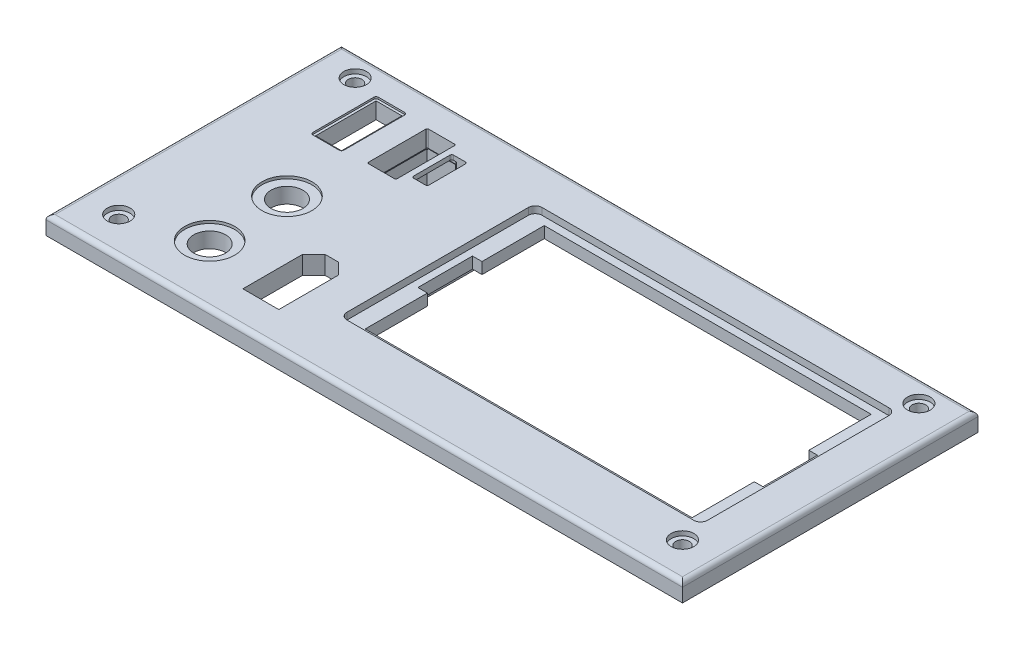
SolidWorks part; units mm, degrees
ref_plane "Спереди" through (0, 0, 0) normal (0, 0, 1) x (1, 0, 0)
ref_plane "Сверху" through (0, 0, 0) normal (0, 1, 0) x (1, 0, 0)
ref_plane "Справа" through (0, 0, 0) normal (1, 0, 0) x (0, 0, -1)
sketch "Эскиз1" plane through (0, 0, 0) normal (0, 1, 0) x (1, 0, 0)
  line L1 (-60, 30) -> (80, 30)
  line L2 (-60, 30) -> (-60, -35)
  line L3 (-60, -35) -> (80, -35)
  line L4 (80, 30) -> (80, -35)
  line L5 (-60, 30) -> (80, -35) construction
  line L6 (-60, -35) -> (80, 30) construction
  point P0 (0, 0)
  dimension "D1" = 65
  dimension "D2" = 140
extrude "Передняя панель основа" add sketch "Эскиз1" along normal blind 4
sketch "Эскиз2" plane through (0, 4, 0) normal (0, 1, 0) x (1, 0, 0)
  line L1 (71, 20.9) -> (-8.3, 20.9)
  line L2 (71, 20.9) -> (71, -22)
  line L3 (71, -22) -> (-8.3, -22)
  line L4 (-8.3, 20.9) -> (-8.3, -22)
  line L5 (71, 20.9) -> (-8.3, -22) construction
  line L6 (71, -22) -> (-8.3, 20.9) construction
  point P0 (31.35, -0.55)
  dimension "D1" = 42.9
  dimension "D2" = 79.3
  dimension "D3" = 13
  dimension "D4" = 9
extrude "Внешняя рамка модуля" cut sketch "Эскиз2" against normal blind 1.5
fillet "Уголки скругления рамки выреза модуля" radius 1.5 4 edges at (71, 3.25, 22) (-8.3, 3.25, 22) (71, 3.25, -20.9) (-8.3, 3.25, -20.9)
sketch "Эскиз3" plane through (0, 2.5, 0) normal (0, 1, 0) x (1, 0, 0)
  line L0 (-60, -35) -> (80, -35) construction
  line L1 (-4.6, 19.2) -> (67.3, 19.2)
  line L2 (-4.6, 19.2) -> (-4.6, -20.2)
  line L3 (-4.6, -20.2) -> (67.3, -20.2)
  line L4 (67.3, 19.2) -> (67.3, -20.2)
  line L5 (-4.6, 19.2) -> (67.3, -20.2) construction
  line L6 (-4.6, -20.2) -> (67.3, 19.2) construction
  line L7 (69.5, 20.9) -> (-6.8, 20.9) construction
  line L8 (-6.8, -22) -> (69.5, -22) construction
  line L9 (71, -20.5) -> (71, 19.4) construction
  line L10 (-8.3, 19.4) -> (-8.3, -20.5) construction
  point P0 (31.35, -0.5)
  dimension "D1" = 39.4
  dimension "D2" = 71.9
  dimension "D3" = 14.8
  dimension "D4" = 12.7
  dimension "D5" = 1.7
  dimension "D6" = 1.8
  dimension "D7" = 3.7
  dimension "D8" = 3.7
extrude "Вырез тела модуля" cut sketch "Эскиз3" against normal blind 3
sketch "Эскиз4" plane through (0, 2.5, 0) normal (0, 1, 0) x (1, 0, 0)
  line L0 (-4.6, 19.2) -> (-4.6, -20.2) construction
  line L1 (-2.5, -6.5) -> (-6.7, -6.5)
  line L2 (-2.5, -6.5) -> (-2.5, 5.5)
  line L3 (-2.5, 5.5) -> (-6.7, 5.5)
  line L4 (-6.7, -6.5) -> (-6.7, 5.5)
  line L5 (-2.5, -6.5) -> (-6.7, 5.5) construction
  line L6 (-2.5, 5.5) -> (-6.7, -6.5) construction
  line L7 (69.2, -6.5) -> (69.2, 5.5)
  line L8 (69.2, -6.5) -> (65, -6.5)
  line L9 (65, -6.5) -> (65, 5.5)
  line L10 (69.2, 5.5) -> (65, 5.5)
  point P0 (-4.6, -0.5)
  dimension "D1" = 12
  dimension "D2" = 4.2
  dimension "D3" = 2
extrude "Ушки модуля" cut sketch "Эскиз4" against normal blind 3
sketch "Эскиз5" plane through (0, 4, 0) normal (0, 1, 0) x (1, 0, 0)
  line L1 (-60, -35) -> (80, -35) construction
  line L2 (-60, 30) -> (-60, -35) construction
  circle A0 centre (-37, -5) radius 5.5
  circle A1 centre (-37, -22) radius 5.5
  dimension "D1" = 11
  dimension "D2" = 11
  dimension "D3" = 13
  dimension "D4" = 23
  dimension "D5" = 17
extrude "Внешние кольца под бананы" cut sketch "Эскиз5" against normal blind 0.6
sketch "Эскиз6" plane through (0, 3.4, 0) normal (0, 1, 0) x (1, 0, 0)
  circle A0 centre (-37, -5) radius 3.5
  circle A1 centre (-37, -22) radius 3.5
  dimension "D1" = 7
  dimension "D2" = 7
extrude "Вырез под бананы" cut sketch "Эскиз6" against normal through all
sketch "Эскиз7" plane through (0, 4, 0) normal (0, 1, 0) x (1, 0, 0)
  line L1 (-46.3, 23.9) -> (-39.5, 23.9)
  line L2 (-46.3, 23.9) -> (-46.3, 9.5)
  line L3 (-46.3, 9.5) -> (-39.5, 9.5)
  line L4 (-39.5, 23.9) -> (-39.5, 9.5)
  line L5 (-46.3, 23.9) -> (-39.5, 9.5) construction
  line L6 (-46.3, 9.5) -> (-39.5, 23.9) construction
  line L10 (-8.3, 19.4) -> (-8.3, -20.5) construction
  line L11 (69.5, 20.9) -> (-6.8, 20.9) construction
  circle A0 centre (-37, -5) radius 5.5 construction
  point P0 (-42.9, 16.7)
  dimension "D1" = 14.4
  dimension "D2" = 6.8
  dimension "D4" = 2.5
extrude "Внешняя рамка USB" cut sketch "Эскиз7" against normal blind 0.4
sketch "Эскиз8" plane through (0, 3.6, 0) normal (0, 1, 0) x (1, 0, 0)
  line L0 (-39.5, 23.9) -> (-46.3, 23.9) construction
  line L1 (-45.75, 23.35) -> (-40.05, 23.35)
  line L2 (-45.75, 23.35) -> (-45.75, 10.05)
  line L3 (-45.75, 10.05) -> (-40.05, 10.05)
  line L4 (-40.05, 23.35) -> (-40.05, 10.05)
  line L5 (-45.75, 23.35) -> (-40.05, 10.05) construction
  line L6 (-45.75, 10.05) -> (-40.05, 23.35) construction
  line L7 (-46.3, 9.5) -> (-39.5, 9.5) construction
  line L8 (-46.3, 23.9) -> (-46.3, 9.5) construction
  line L9 (-39.5, 9.5) -> (-39.5, 23.9) construction
  point P0 (-42.9, 16.7)
  dimension "D1" = 13.3
  dimension "D2" = 5.7
  dimension "D3" = 0.55
  dimension "D4" = 0.55
  dimension "D5" = 0.55
  dimension "D6" = 0.55
extrude "USB" cut sketch "Эскиз8" against normal through all
fillet "Скругление уголков 1 USB" radius 0.5 4 edges at (-46.3, 3.8, -9.5) (-39.5, 3.8, -9.5) (-39.5, 3.8, -23.9) (-46.3, 3.8, -23.9)
sketch "Эскиз9" plane through (0, 4, 0) normal (0, 1, 0) x (1, 0, 0)
  line L0 (-24.2, -27.5) -> (-16.3, -27.5)
  line L1 (-16.3, -27.5) -> (-16.3, -14.4)
  line L2 (-16.3, -14.4) -> (-18.8, -11.9)
  line L3 (-18.8, -11.9) -> (-21.7, -11.9)
  line L4 (-21.7, -11.9) -> (-24.2, -14.4)
  line L5 (-24.2, -14.4) -> (-24.2, -27.5)
  line L6 (-46.3, 23.4) -> (-46.3, 10) construction
  line L7 (-60, -35) -> (80, -35) construction
  line L8 (-8.3, 19.4) -> (-8.3, -20.5) construction
  line L9 (-60, 30) -> (-60, -35) construction
  circle A3 centre (-37, -22) radius 5.5 construction
  point P8 (-20.25, -27.5)
  point P9 (-20.25, -11.9)
  dimension "D4" = 7.5
  dimension "D1" = 7.9
  dimension "D2" = 15.6
  dimension "D3" = 2.5
  dimension "D5" = 8
  dimension "D6" = 12.8
  dimension "D7" = 35.8
extrude "XT60 на передней панели" cut sketch "Эскиз9" against normal through all
sketch "Эскиз10" plane through (0, 4, 0) normal (0, 1, 0) x (1, 0, 0)
  line L0 (80, 30) -> (-60, 30) construction
  line L1 (-60, 30) -> (-60, -35) construction
  line L2 (80, -35) -> (80, 30) construction
  line L3 (-60, -35) -> (80, -35) construction
  circle A0 centre (-52, 25) radius 1.5
  circle A1 centre (72, 25) radius 1.5
  circle A2 centre (72, -27) radius 1.5
  circle A3 centre (-52, -27) radius 1.5
  dimension "D1" = 3
  dimension "D2" = 5
  dimension "D3" = 8
  dimension "D5" = 8
  dimension "D6" = 5
  dimension "D7" = 8
  dimension "D8" = 8
  dimension "D9" = 8
  dimension "D10" = 8
  dimension "D4" = 2
extrude "Отверстия крепления передней панели к корпусу" cut sketch "Эскиз10" against normal through all
sketch "Эскиз13" plane through (0, 4, 0) normal (0, 1, 0) x (1, 0, 0)
  circle A0 centre (-52, 25) radius 2.5
  circle A1 centre (72, 25) radius 2.5
  circle A2 centre (72, -27) radius 2.5
  circle A3 centre (-52, -27) radius 2.5
  dimension "D1" = 5
  dimension "D2" = 2
extrude "Фаска под головку болта передней панели" cut sketch "Эскиз13" against normal blind 1
fillet "Скругление1" radius 1 4 edges at (10, 4, 35) (80, 4, 2.5) (-60, 4, 2.5) (10, 4, -30)
sketch "Эскиз14" plane through (0, 4, 0) normal (0, 1, 0) x (1, 0, 0)
  line L0 (-28.2, 10.15) -> (-34.5, 10.15)
  line L1 (-34.5, 10.15) -> (-34.5, 23.35)
  line L2 (-34.5, 23.35) -> (-28.2, 23.35)
  line L3 (-28.2, 23.35) -> (-28.2, 25.9)
  line L4 (-28.2, 25.9) -> (-26.9, 25.9)
  line L5 (-26.9, 25.9) -> (-26.9, 21.15)
  line L6 (-26.9, 21.15) -> (-23.5, 21.15)
  line L7 (-23.5, 21.15) -> (-23.5, 12.35)
  line L8 (-23.5, 12.35) -> (-26.9, 12.35)
  line L9 (-26.9, 12.35) -> (-26.9, 7.6)
  line L10 (-26.9, 7.6) -> (-28.2, 7.6)
  line L11 (-28.2, 7.6) -> (-28.2, 10.15)
  line L12 (-40.05, 23.35) -> (-45.75, 23.35) construction
  circle A0 centre (-37, -5) radius 3.5 construction
  dimension "D1" = 13.2
  dimension "D2" = 11
  dimension "D3" = 6.3
  dimension "D4" = 1.3
  dimension "D5" = 3.4
  dimension "D6" = 8.8
  dimension "D7" = 18.3
  dimension "D8" = 2.5
extrude "Вырез-Вытянуть1" cut sketch "Эскиз14" against normal through all
fillet "Скругление2" radius 0.4 2 edges at (-23.5, 2, -12.35) (-23.5, 2, -21.15)
fillet "Скругление3" radius 0.3 2 edges at (-34.5, 2, -10.15) (-34.5, 2, -23.35)
sketch "Эскиз15" plane through (0, 4, 0) normal (0, 1, 0) x (1, 0, 0)
  line L1 (-28.2, 26) -> (-26.9, 26)
  line L2 (-28.2, 26) -> (-28.2, 7.6)
  line L3 (-28.2, 7.6) -> (-26.9, 7.6)
  line L4 (-26.9, 26) -> (-26.9, 7.6)
  line L5 (-28.2, 26) -> (-26.9, 7.6) construction
  line L6 (-28.2, 7.6) -> (-26.9, 26) construction
  line L11 (-26.9, 25.9) -> (-28.2, 25.9) construction
  line L12 (-28.2, 7.6) -> (-26.9, 7.6) construction
  line L15 (-28.2, 25.9) -> (-28.2, 23.35) construction
  point P0 (-27.55, 16.8)
  point P10 (-27.55, 7.6)
  dimension "D1" = 18.4
extrude "Бобышка-Вытянуть1" add sketch "Эскиз15" against normal blind 1
fillet "Скругление4" radius 0.3 2 edges at (-28.2, 3.5, -10.15) (-28.2, 3.5, -23.35)
fillet "Скругление5" radius 0.4 2 edges at (-26.9, 3.5, -12.35) (-26.9, 3.5, -21.15)
sketch "Эскиз17" plane through (0, 0, 0) normal (0, -1, 0) x (1, 0, 0)
  line L0 (-34.6184, -9.9961) -> (-28.3093, -9.9961)
  line L1 (-28.3093, -9.9961) -> (-28.3093, -7.5533)
  line L2 (-28.3093, -7.5533) -> (-25.8093, -7.5533)
  line L3 (-25.8093, -7.5533) -> (-25.8093, -12.1697)
  line L4 (-25.8093, -12.1697) -> (-23.3093, -12.1697)
  line L5 (-23.3093, -12.1697) -> (-23.3093, -21.2455)
  line L6 (-23.3093, -21.2455) -> (-25.8093, -21.2455)
  line L7 (-25.8093, -21.2455) -> (-25.8093, -25.9546)
  line L8 (-25.8093, -25.9546) -> (-28.3093, -25.9546)
  line L9 (-28.3093, -25.9546) -> (-28.3093, -23.4086)
  line L10 (-28.3093, -23.4086) -> (-34.6184, -23.4086)
  line L11 (-34.6184, -23.4086) -> (-34.6184, -9.9961)
extrude "Вытянуть-Тонкостенный1" add sketch "Эскиз17" along normal blind 15 thin thin type one direction wall 2
fillet "Скругление6" radius 0.5 12 edges at (-23.8093, -7.5, -23.2455) (-23.8093, -7.5, -27.9546) (-30.3093, -7.5, -27.9546) (-30.3093, -7.5, -25.4086) (-36.6184, -7.5, -25.4086) (-36.6184, -7.5, -7.9961) (-30.3093, -7.5, -7.9961) (-30.3093, -7.5, -5.5533) (-21.3093, -7.5, -23.2455) (-23.8093, -7.5, -10.1697) (-21.3093, -7.5, -10.1697) (-23.8093, -7.5, -5.5533)
sketch "Эскиз18" plane through (0, 0, 0) normal (0, -1, 0) x (1, 0, 0)
  line L1 (-25.8093, -7.5533) -> (-26.9, -7.5533)
  line L2 (-25.8093, -7.5533) -> (-25.8093, -25.9)
  line L3 (-25.8093, -25.9) -> (-26.9, -25.9)
  line L4 (-26.9, -7.5533) -> (-26.9, -25.9)
extrude "Вырез-Вытянуть2" cut sketch "Эскиз18" against normal blind 3
chamfer "Фаска1" distance 0.3 angle 20 7 edges at (-31.2, 0, -23.35) (-34.4121, 0, -23.2621) (-34.5, 0, -16.75) (-34.4121, 0, -10.2379) (-27.55, 0, -7.6) (-28.2, 0, -8.875) (-31.2, 0, -10.15) first distance on face at (-30.3, 2.3333, -23.35) first distance on face at (-34.3811, 2, -23.2311) first distance on face at (-34.5, 2, -16.75) first distance on face at (-34.3811, 2, -10.2689) first distance on face at (-27.55, 1.5, -7.6) first distance on face at (-28.2, 1.5, -8.875) first distance on face at (-30.3, 2.3333, -10.15)
chamfer "Фаска2" distance 0.3 angle 25 5 edges at (-24.8547, 0, -12.35) (-24.8547, 0, -21.15) (-23.6172, 0, -12.4672) (-23.6172, 0, -21.0328) (-23.5, 0, -16.75) first distance on face at (-25.4031, 2.3333, -12.35) first distance on face at (-25.4031, 2.3333, -21.15) first distance on face at (-23.6586, 2, -12.5086) first distance on face at (-23.6586, 2, -20.9914) first distance on face at (-23.5, 2, -16.75)
chamfer "Фаска3" distance 0.3 angle 25 2 edges at (-27.0047, 0, -25.9) (-28.2, 0, -24.6796) first distance on face at (-27.0047, 1.5, -25.9) first distance on face at (-28.2, 1.26, -24.3918)
chamfer "Фаска4" distance 0.3 angle 25 4 edges at (-24.8547, 0, -12.2101) (-23.5182, 0, -12.3682) (-23.3601, 0, -16.75) (-23.4488, 0, -21.0465) first distance on face at (-24.8547, 0.15, -12.2801) first distance on face at (-23.6164, 0.15, -12.4664) first distance on face at (-23.4301, 0.15, -16.75) first distance on face at (-23.6375, 0.1435, -21.0545)
